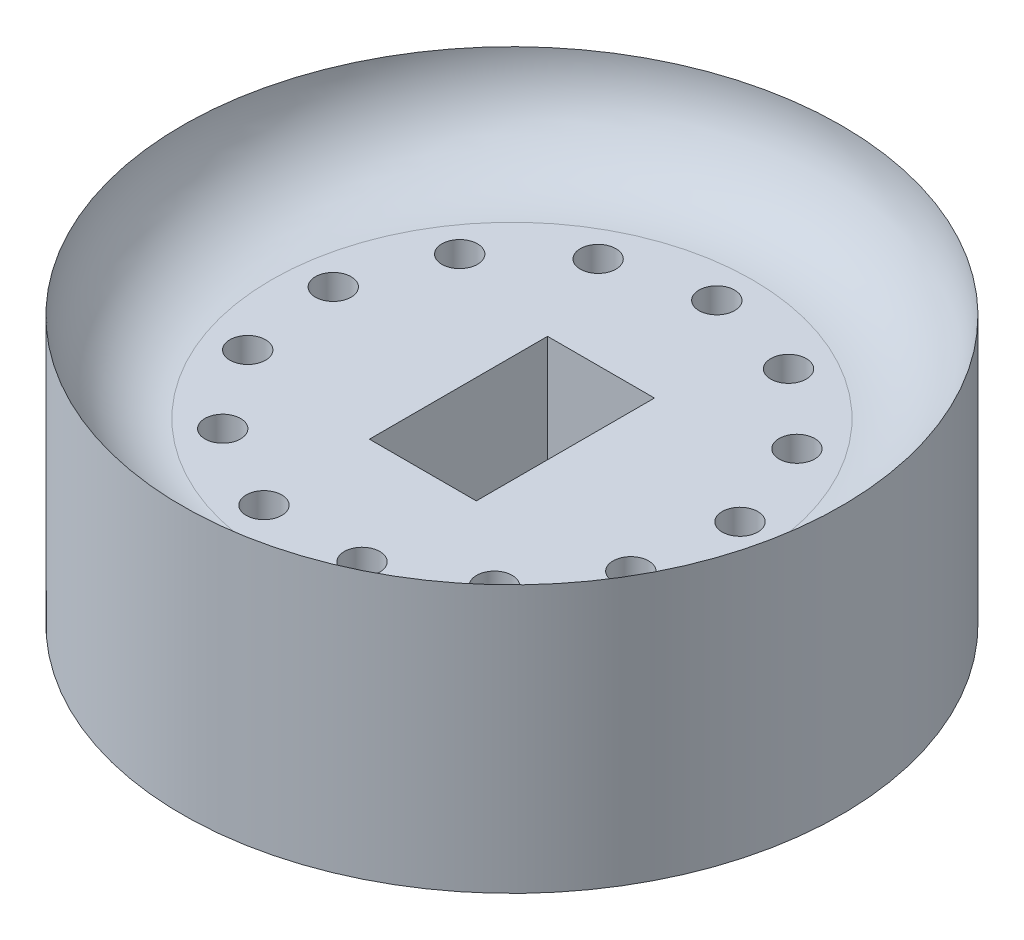
SolidWorks part; units mm, degrees
ref_plane "Alzado" through (0, 0, 0) normal (0, 0, 1) x (1, 0, 0)
ref_plane "Planta" through (0, 0, 0) normal (0, 1, 0) x (1, 0, 0)
ref_plane "Vista lateral" through (0, 0, 0) normal (1, 0, 0) x (0, 0, -1)
sketch "Croquis1" plane through (0, 0, 0) normal (0, 0, 1) x (1, 0, 0)
  line L0 (6.75, 5) -> (0, 5)
  line L1 (0, 0) -> (9.25, 0)
  line L2 (0, 0) -> (0, 7.5)
  line L3 (0, 7.5) -> (9.25, 7.5)
  line L4 (9.25, 0) -> (9.25, 7.5)
  circle A0 centre (6.75, 7.5) radius 2.5
  dimension "D1" = 9.25
  dimension "D2" = 7.5
  dimension "D3" = 2.5
revolve "Revolución1" add sketch "Croquis1" angle 360 about L2 region at (4.7396, 2.5862, 0)
sketch "Croquis2" plane through (0, 5, 0) normal (0, 1, 0) x (1, 0, 0)
  line L1 (-1.5, -2.5) -> (1.5, -2.5)
  line L2 (-1.5, -2.5) -> (-1.5, 2.5)
  line L3 (-1.5, 2.5) -> (1.5, 2.5)
  line L4 (1.5, -2.5) -> (1.5, 2.5)
  line L5 (-1.5, -2.5) -> (1.5, 2.5) construction
  line L6 (-1.5, 2.5) -> (1.5, -2.5) construction
  circle A0 centre (0, 5.75) radius 0.5
  circle A1 centre (2.6722, 5.0914) radius 0.5
  circle A2 centre (4.7322, 3.2664) radius 0.5
  circle A3 centre (5.7081, 0.6931) radius 0.5
  circle A4 centre (5.3763, -2.039) radius 0.5
  circle A5 centre (3.813, -4.3039) radius 0.5
  circle A6 centre (1.3761, -5.5829) radius 0.5
  circle A7 centre (-1.3761, -5.5829) radius 0.5
  circle A8 centre (-3.813, -4.3039) radius 0.5
  circle A9 centre (-5.3763, -2.039) radius 0.5
  circle A10 centre (-5.7081, 0.6931) radius 0.5
  circle A11 centre (-4.7322, 3.2664) radius 0.5
  circle A12 centre (-2.6722, 5.0914) radius 0.5
  point P2 (0, 0)
  point P29 (0, 0)
  dimension "D1" = 1
  dimension "D3" = 3
  dimension "D4" = 5
  dimension "D5" = 5.75
  dimension "D2" = 13
extrude "Cortar-Extruir1" cut sketch "Croquis2" against normal through all
